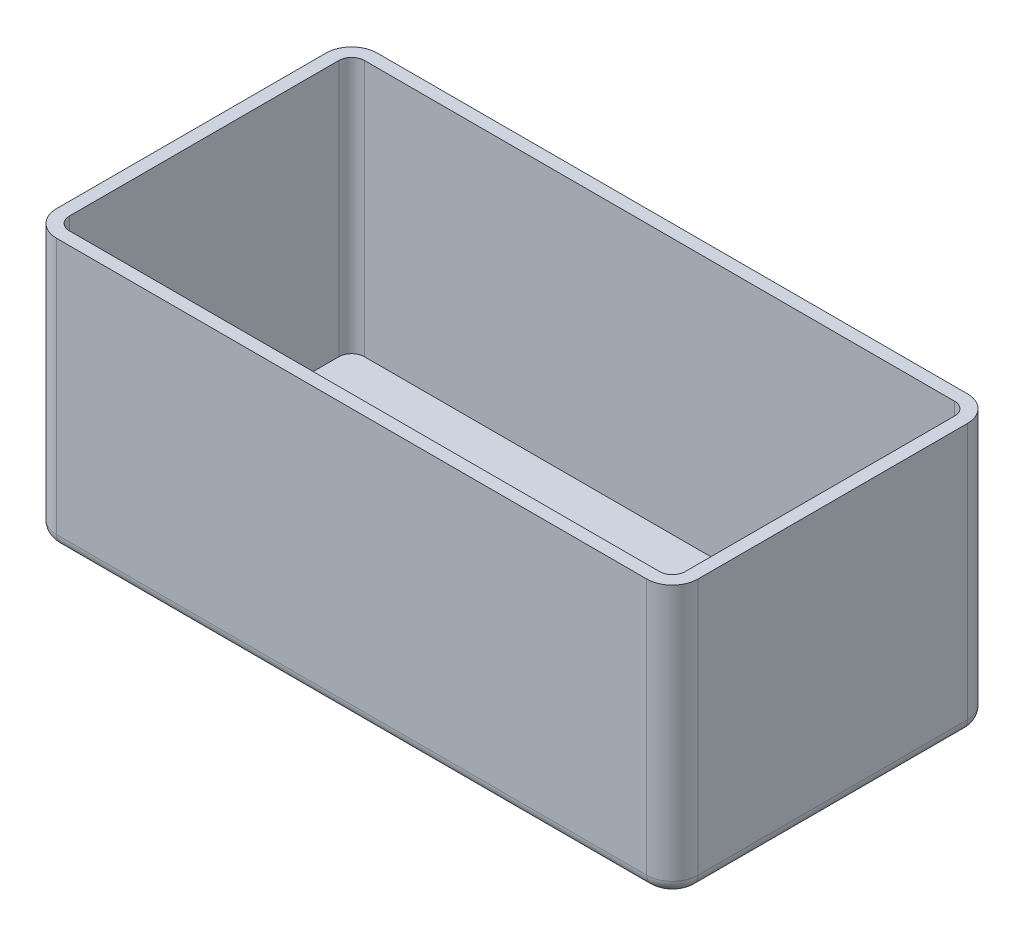
SolidWorks part; units mm, degrees
ref_plane "Front Plane" through (0, 0, 0) normal (0, 0, 1) x (1, 0, 0)
ref_plane "Top Plane" through (0, 0, 0) normal (0, 1, 0) x (1, 0, 0)
ref_plane "Right Plane" through (0, 0, 0) normal (1, 0, 0) x (0, 0, -1)
sketch "Sketch1" plane through (0, 0, 0) normal (0, 1, 0) x (1, 0, 0)
  line L1 (-115, -62.5) -> (115, -62.5)
  line L2 (-125, -52.5) -> (-125, 52.5)
  line L3 (-115, 62.5) -> (115, 62.5)
  line L4 (125, -52.5) -> (125, 52.5)
  line L5 (-125, -62.5) -> (125, 62.5) construction
  line L6 (-125, 62.5) -> (125, -62.5) construction
  arc A0 (-115, -62.5) -> (-125, -52.5) centre (-115, -52.5) cw
  arc A1 (115, -62.5) -> (125, -52.5) centre (115, -52.5) ccw
  arc A2 (115, 62.5) -> (125, 52.5) centre (115, 52.5) cw
  arc A3 (-125, 52.5) -> (-115, 62.5) centre (-115, 52.5) cw
  point P0 (0, 0)
  dimension "D3" = 10
  dimension "D1" = 250
  dimension "D2" = 125
extrude "Boss-Extrude1" add sketch "Sketch1" along normal blind 5
fillet "Fillet1" radius 5 8 edges at (0, 0, 62.5) (122.0711, 0, 59.5711) (125, 0, 0) (122.0711, 0, -59.5711) (0, 0, -62.5) (-122.0711, 0, -59.5711) (-125, 0, 0) (-122.0711, 0, 59.5711)
sketch "Sketch2" plane through (0, 5, 0) normal (0, 1, 0) x (1, 0, 0)
  line L0 (-115, -57.5) -> (115, -57.5)
  line L1 (120, -52.5) -> (120, 52.5)
  line L2 (115, 57.5) -> (-115, 57.5)
  line L3 (-120, 52.5) -> (-120, -52.5)
  line L4 (-115, -62.5) -> (115, -62.5)
  line L5 (-115, -62.5) -> (115, -62.5)
  line L6 (125, -52.5) -> (125, 52.5)
  line L7 (125, -52.5) -> (125, 52.5)
  line L16 (115, 62.5) -> (-115, 62.5)
  line L17 (115, 62.5) -> (-115, 62.5)
  line L18 (-125, 52.5) -> (-125, -52.5)
  line L19 (-125, 52.5) -> (-125, -52.5)
  arc A0 (115, -57.5) -> (120, -52.5) centre (115, -52.5) ccw
  arc A1 (120, 52.5) -> (115, 57.5) centre (115, 52.5) ccw
  arc A2 (-115, 57.5) -> (-120, 52.5) centre (-115, 52.5) ccw
  arc A3 (-120, -52.5) -> (-115, -57.5) centre (-115, -52.5) ccw
  arc A4 (-125, -52.5) -> (-115, -62.5) centre (-115, -52.5) ccw
  arc A5 (-125, -52.5) -> (-115, -62.5) centre (-115, -52.5) ccw
  arc A6 (115, -62.5) -> (125, -52.5) centre (115, -52.5) ccw
  arc A7 (115, -62.5) -> (125, -52.5) centre (115, -52.5) ccw
  arc A16 (125, 52.5) -> (115, 62.5) centre (115, 52.5) ccw
  arc A17 (125, 52.5) -> (115, 62.5) centre (115, 52.5) ccw
  arc A18 (-115, 62.5) -> (-125, 52.5) centre (-115, 52.5) ccw
  arc A19 (-115, 62.5) -> (-125, 52.5) centre (-115, 52.5) ccw
extrude "Boss-Extrude2" add sketch "Sketch2" along normal blind 100
equation "\"device_length\"=250"
equation "\"D1@Sketch1\"=\"device_length\""
equation "\"device_width\"=125"
equation "\"D2@Sketch1\"=\"device_width\""
equation "\"device_wall\"= 5"
equation "\"D2@Sketch2\"=\"device_wall\""
equation "\"device_base\"= 5"
equation "\"D1@Boss-Extrude1\"=\"device_base\""
equation "\"D1@Fillet1\"=\"device_base\""
